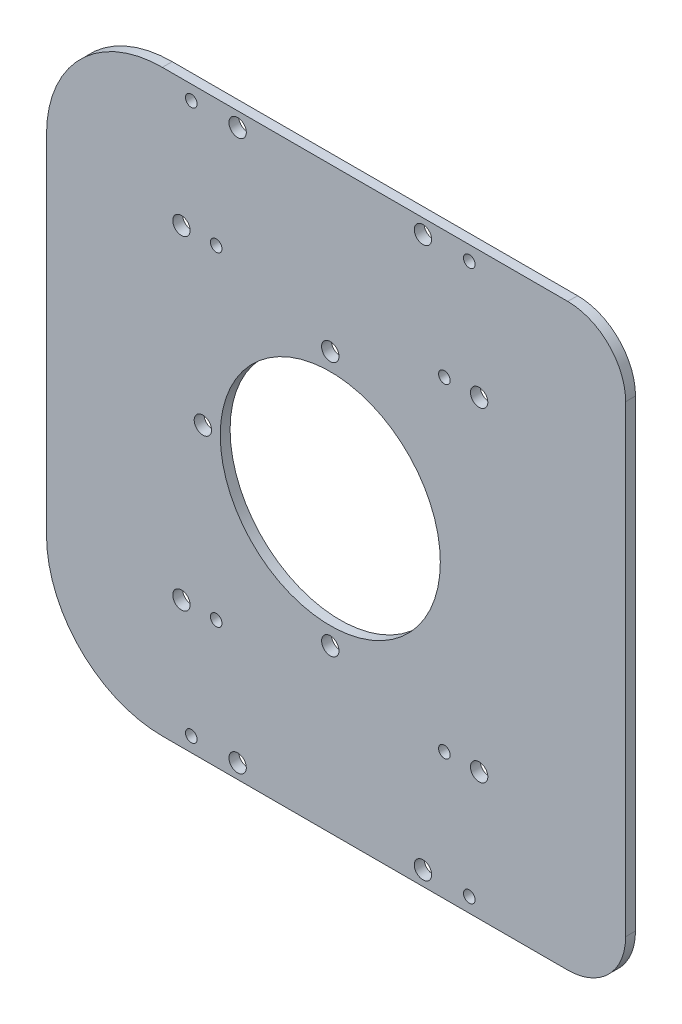
SolidWorks part; units mm, degrees
ref_plane "前视基准面" through (0, 0, 0) normal (0, 0, 1) x (1, 0, 0)
ref_plane "上视基准面" through (0, 0, 0) normal (0, 1, 0) x (1, 0, 0)
ref_plane "右视基准面" through (0, 0, 0) normal (1, 0, 0) x (0, 0, -1)
other "Configuration Table"
sketch "草图1" plane through (0, 0, 0) normal (0, 0, 1) x (1, 0, 0)
  line L0 (0, 0) -> (40.5006, 0) construction
  line L1 (-29, 50) -> (29, 50)
  line L2 (-29, 50) -> (-29, -50)
  line L3 (-29, -50) -> (29, -50)
  line L4 (29, 50) -> (29, -50)
  line L5 (-29, 50) -> (29, -50) construction
  line L6 (-29, -50) -> (29, 50) construction
  line L7 (0, 0) -> (0, 25.3918) construction
  line L8 (-16, 47.5) -> (-15.2, 47.5) construction
  line L9 (-15.2, 47.5) -> (-15.2, 40.4726) construction
  line L10 (15.2, 47.5) -> (15.2, 40.4726) construction
  circle A0 centre (-24, 47.5) radius 1
  circle A1 centre (-16, 47.5) radius 1.5
  circle A4 centre (16, 47.5) radius 1.5
  circle A5 centre (24, 47.5) radius 1
  circle A7 centre (-19.7, 28) radius 1
  circle A8 centre (-25.7, 28) radius 1.5
  circle A10 centre (19.7, 28) radius 1
  circle A11 centre (25.7, 28) radius 1.5
  circle A12 centre (25.7, -28) radius 1.5
  circle A13 centre (24, -47.5) radius 1
  circle A14 centre (16, -47.5) radius 1.5
  circle A15 centre (19.7, -28) radius 1
  circle A20 centre (-19.7, -28) radius 1
  circle A21 centre (-25.7, -28) radius 1.5
  circle A22 centre (-24, -47.5) radius 1
  circle A23 centre (-16, -47.5) radius 1.5
  point P0 (0, 0)
  dimension "D3" = 2
  dimension "D4" = 3
  dimension "D5" = 4.5
  dimension "D14" = 2
  dimension "D16" = 3
  dimension "D1" = 100
  dimension "D2" = 58
  dimension "D6" = 2.5
  dimension "D7" = 19.5
  dimension "D8" = 16
  dimension "D9" = 24
  dimension "D10" = 0.8
  dimension "D17" = 6
extrude "凸台-拉伸1" add sketch "草图1" along normal blind 3
sketch "草图2" plane through (0, 0, 3) normal (0, 0, 1) x (1, 0, 0)
  line L0 (29, 50) -> (-29, 50) construction
  line L1 (-49, 50) -> (51, 50)
  line L2 (-49, 50) -> (-49, -50)
  line L3 (-49, -50) -> (51, -50)
  line L4 (51, 50) -> (51, -50)
  line L5 (-29, -50) -> (29, -50) construction
  line L6 (-29, 50) -> (-29, -50) construction
  circle A0 centre (0, 0) radius 19
  circle A1 centre (0, 22) radius 1.5
  circle A2 centre (-22, 0) radius 1.5
  circle A3 centre (0, -22) radius 1.5
  point P19 (0, 0)
  point P20 (0, 0)
  point P21 (0, 0)
  point P22 (0, 0)
  point P23 (0, 0)
  line M13 (29, -50) -> (29, 50)
  line M15 (-29, 50) -> (-29, -50)
  dimension "D3" = 38
  dimension "D4" = 3
  dimension "D1" = 20
  dimension "D2" = 100
  dimension "D5" = 22
  dimension "D6" = 22
  dimension "D7" = 22
extrude "切除-拉伸1" cut sketch "草图2" against normal blind 10 contours A3 | A2 | A1 | A0 region at (0, 0, 3) region at (0, 22, 3) region at (-22, 0, 3) region at (0, -22, 3)
extrude "凸台-拉伸2" add sketch "草图2<3>" against normal blind 3 contours L2 L3 L1 M15 | L4 L1 L3 M13 region at (-39, 0, 3) region at (40, 0, 3)
sketch "草图2<3>" plane through (0, 0, 3) normal (0, 0, 1) x (1, 0, 0) same geometry as "草图2"
fillet "圆角1" radius 20 2 edges at (-49, 50, 1.5) (-49, -50, 1.5)
fillet "圆角2" radius 10 2 edges at (51, 50, 1.5) (51, -50, 1.5)
sketch "草图3" plane through (0, 0, 0) normal (0, 0, -1) x (-1, 0, 0)
  line L4 (29, 50) -> (-41, 50)
  line L5 (-51, 40) -> (-51, -40)
  line L6 (-41, -50) -> (29, -50)
  line L7 (49, -30) -> (49, 30)
  line L8 (29, 50) -> (-41, 50)
  line L9 (-51, 40) -> (-51, -40)
  line L10 (-41, -50) -> (29, -50)
  line L11 (49, -30) -> (49, 30)
  arc A4 (-41, 50) -> (-51, 40) centre (-41, 40) ccw
  arc A5 (-51, -40) -> (-41, -50) centre (-41, -40) ccw
  arc A6 (29, -50) -> (49, -30) centre (29, -30) ccw
  arc A7 (49, 30) -> (29, 50) centre (29, 30) ccw
  arc A8 (-41, 50) -> (-51, 40) centre (-41, 40) ccw
  arc A9 (-51, -40) -> (-41, -50) centre (-41, -40) ccw
  arc A10 (29, -50) -> (49, -30) centre (29, -30) ccw
  arc A11 (49, 30) -> (29, 50) centre (29, 30) ccw
  dimension "D1" = 0
extrude "切除-拉伸2" cut sketch "草图3" against normal blind 1.3
